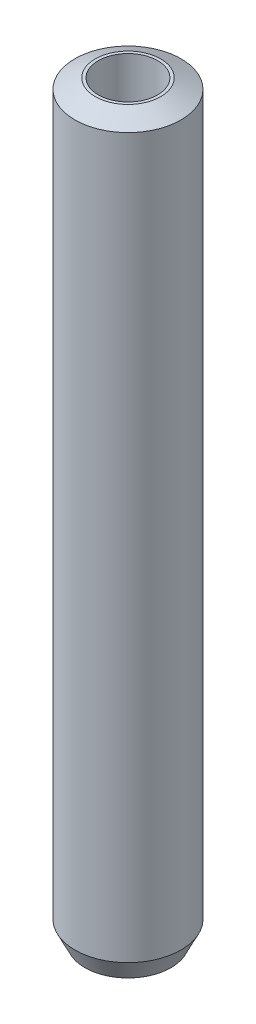
SolidWorks part; units mm, degrees
ref_plane "Front Plane" through (0, 0, 0) normal (0, 0, 1) x (1, 0, 0)
ref_plane "Top Plane" through (0, 0, 0) normal (0, 1, 0) x (1, 0, 0)
ref_plane "Right Plane" through (0, 0, 0) normal (1, 0, 0) x (0, 0, -1)
sketch "Sketch1" plane through (0, 0, 0) normal (0, 1, 0) x (1, 0, 0)
  circle A0 centre (0, 0) radius 15
  dimension "SHAFT_OD" = 30
extrude "Boss-Extrude1" add sketch "Sketch1" along normal blind 211.8311
sketch "Sketch2" plane through (0, 0, 0) normal (0, 1, 0) x (1, 0, 0)
  circle A0 centre (0, 0) radius 8.3929
  dimension "BORE_D" = 16.7858
extrude "Cut-Extrude1" cut sketch "Sketch2" along normal through all
chamfer "Chamfer1" distance 2.827 angle 63.82 2 edges at (0, 211.8311, 15) (0, 0, 15) first distance on face at (0, 211.8311, 15) first distance on face at (0, 0, 8.3929)
